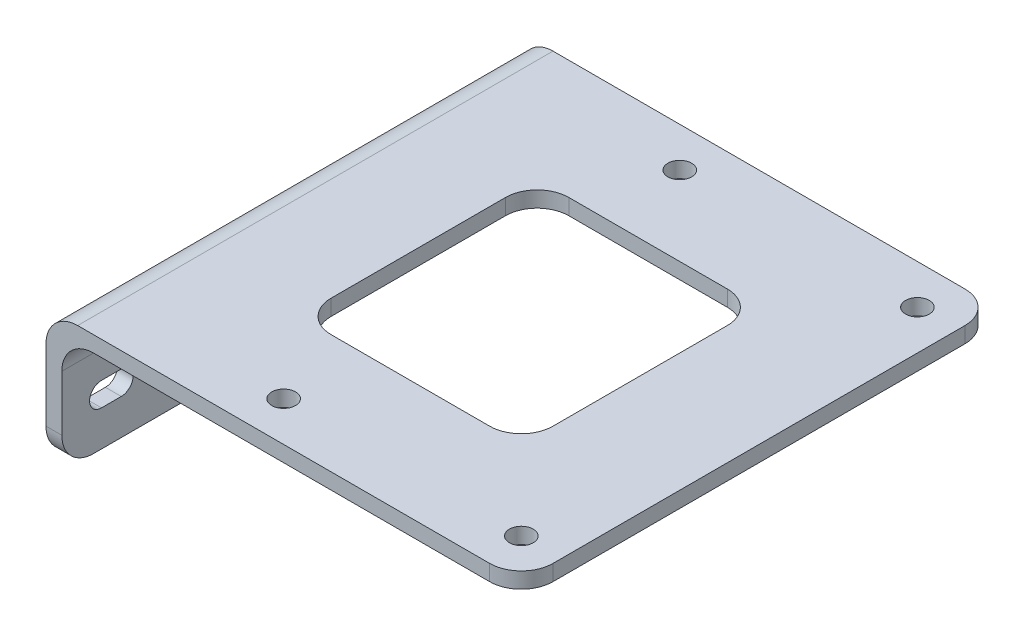
SolidWorks part; units mm, degrees
ref_plane "前视基准面" through (0, 0, 0) normal (0, 0, 1) x (1, 0, 0)
ref_plane "上视基准面" through (0, 0, 0) normal (0, 1, 0) x (1, 0, 0)
ref_plane "右视基准面" through (0, 0, 0) normal (1, 0, 0) x (0, 0, -1)
other "Configuration Table"
sketch "草图1" plane through (0, 0, 0) normal (0, 1, 0) x (1, 0, 0)
  line L0 (-611.6962, 0) -> (29973.1156, 0) construction
  line L1 (-20, -30) -> (20, -30)
  line L2 (-20, -30) -> (-20, 30)
  line L3 (-20, 30) -> (20, 30)
  line L4 (20, -30) -> (20, 30)
  line L5 (-20, -30) -> (20, 30) construction
  line L6 (-20, 30) -> (20, -30) construction
  line L7 (0, -611.6962) -> (0, 29973.1156) construction
  circle A0 centre (-15, 25) radius 1.5
  circle A1 centre (15, 25) radius 1.5
  circle A2 centre (15, -25) radius 1.5
  circle A3 centre (-15, -25) radius 1.5
  point P0 (0, 0)
  dimension "D3" = 15
  dimension "D4" = 25
  dimension "D5" = 3
  dimension "D1" = 40
  dimension "D2" = 60
extrude "凸台-拉伸1" add sketch "草图1" along normal blind 2
sketch "草图2" plane through (-20, 0, 0) normal (-1, 0, 0) x (0, 0, 1)
  line L1 (-30, 2) -> (30, 2)
  line L2 (-30, 2) -> (-30, 0)
  line L3 (-30, 0) -> (30, 0)
  line L4 (30, 2) -> (30, 0)
extrude "凸台-拉伸2" add sketch "草图2" along normal blind 20
sketch "草图3" plane through (0, 0, 0) normal (0, -1, 0) x (1, 0, 0)
  line L0 (20, -30) -> (-40, -30) construction
  line L1 (-40, 30) -> (-38, 30)
  line L2 (-40, 30) -> (-40, -30)
  line L3 (-40, -30) -> (-38, -30)
  line L4 (-38, 30) -> (-38, -30)
  dimension "D1" = 2
extrude "凸台-拉伸3" add sketch "草图3" along normal blind 15
fillet "圆角1" radius 4 6 edges at (-40, 2, 0) (-38, 0, 0) (-39, -15, -30) (-39, -15, 30) (20, 1, -30) (20, 1, 30)
sketch "草图6" plane through (-40, 0, 0) normal (-1, 0, 0) x (0, 0, 1)
  line L0 (0, -1000) -> (0, 49000) construction
  line L1 (-25, -9) -> (-22.5, -9) construction
  line L2 (-25, -7.5) -> (-22.5, -7.5)
  line L3 (-25, -10.5) -> (-22.5, -10.5)
  line L5 (26, -15) -> (-26, -15) construction
  line L6 (25, -9) -> (22.5, -9) construction
  line L7 (25, -7.5) -> (22.5, -7.5)
  line L8 (25, -10.5) -> (22.5, -10.5)
  arc A2 (-25, -7.5) -> (-25, -10.5) centre (-25, -9) ccw
  arc A3 (-22.5, -10.5) -> (-22.5, -7.5) centre (-22.5, -9) ccw
  arc A4 (25, -7.5) -> (25, -10.5) centre (25, -9) cw
  arc A5 (22.5, -10.5) -> (22.5, -7.5) centre (22.5, -9) cw
  point P5 (-23.75, -9)
  point P14 (23.75, -9)
  dimension "D1" = 22.5
  dimension "D2" = 25
  dimension "D3" = 1.5
  dimension "D4" = 6
extrude "切除-拉伸1" cut sketch "草图6" against normal through all
sketch "草图7" plane through (0, 2, 0) normal (0, 1, 0) x (1, 0, 0)
  line L0 (20, -26) -> (20, 26) construction
  line L1 (-23, 15) -> (5, 15)
  line L2 (-23, 15) -> (-23, -15)
  line L3 (-23, -15) -> (5, -15)
  line L4 (5, 15) -> (5, -15)
  line L5 (16, 30) -> (-36, 30) construction
  line L6 (-36, 30) -> (-36, -30) construction
  point P4 (5, 0)
  dimension "D1" = 0
  dimension "D2" = 15
  dimension "D3" = 15
  dimension "D4" = 13
extrude "切除-拉伸2" cut sketch "草图7" against normal through all
fillet "圆角3" radius 4 4 edges at (-23, 1, 15) (5, 1, 15) (5, 1, -15) (-23, 1, -15)
